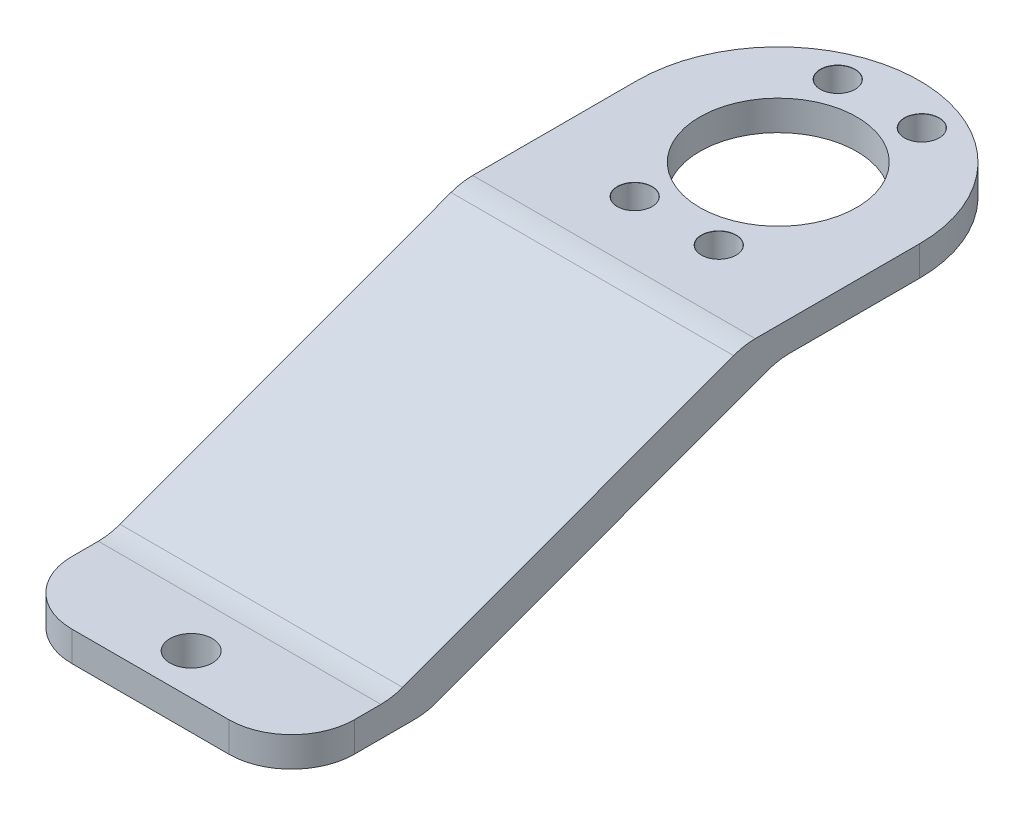
SolidWorks part; units mm, degrees
material "ABS PC"
ref_plane "Front Plane" through (0, 0, 0) normal (0, 0, 1) x (1, 0, 0)
ref_plane "Top Plane" through (0, 0, 0) normal (0, 1, 0) x (1, 0, 0)
ref_plane "Right Plane" through (0, 0, 0) normal (1, 0, 0) x (0, 0, -1)
sketch "Sketch1" plane through (0, 0, 0) normal (0, 1, 0) x (1, 0, 0)
  line L5 (-22.5, -100) -> (22.5, -100)
  line L6 (-22.5, -100) -> (-22.5, 0)
  line L8 (22.5, -100) -> (22.5, 0)
  line L9 (-22.5, -100) -> (22.5, 0) construction
  line L10 (-22.5, 0) -> (22.5, -100) construction
  arc A0 (22.5, 0) -> (-22.5, 0) centre (0, 0) ccw
  point P2 (0, -50)
  dimension "D1" = 45
  dimension "D2" = 100
  dimension "D3" = 45
extrude "Boss-Extrude1" add sketch "Sketch1" along normal blind 25.4
sketch "Sketch2" plane through (0, 25.4, 0) normal (0, 1, 0) x (1, 0, 0)
  line L0 (-6.697, 16.1679) -> (6.697, 16.1679) construction
  circle A0 centre (0, 0) radius 17.5 construction
  circle A1 centre (0, 0) radius 17.5 construction
  circle A2 centre (0, 0) radius 17.5 construction
  circle A3 centre (0, 0) radius 17.5 construction
  circle A4 centre (0, 0) radius 17.5 construction
  circle A5 centre (0, 0) radius 17.5 construction
  circle A6 centre (0, 0) radius 17.5 construction
  circle A7 centre (0, 0) radius 17.5 construction
  point P3 (-6.697, 16.1679)
  point P5 (-16.1679, -6.697)
  point P7 (6.697, 16.1679)
  point P9 (16.1679, 6.697)
  point P11 (16.1679, -6.697)
  point P13 (6.697, -16.1679)
  point P15 (-6.697, -16.1679)
  point P16 (0, 0)
  point P18 (-16.1679, 6.697)
  dimension "D1" = 35
  dimension "D2" = 8
hole_wizard "M5 Clearance Hole1" positions "Sketch3" profile "Sketch4" hole size "M5" standard "ANSI Metric" end condition through all
sketch "Sketch3" plane through (0, 25.4, 0) normal (0, 1, 0) x (1, 0, 0)
  point P0 (-6.697, -16.1679)
  point P3 (6.697, -16.1679)
  point P6 (6.697, 16.1679)
  point P15 (-6.697, 16.1679)
sketch "Sketch4" plane through (-6.697, 25.4, 16.1679) normal (1, 0, 0) x (0, 0, 1)
  line L0 (0, 0) -> (0, 25.4)
  line L1 (0, 25.4) -> (2.75, 25.4)
  line L2 (2.75, 25.4) -> (2.75, 0.025)
  line L3 (2.75, 0.025) -> (2.775, 0)
  line L5 (2.775, 0) -> (0, 0)
  line L6 (-2.75, 0.025) -> (-2.775, 0) construction
  line L11 (0, -6.35) -> (0, 107.95) construction
  dimension "Thru Hole Dia." = 5.5
  dimension "Thru Hole Depth" = 25.4
  dimension "Near C'Sink Dia." = 5.55
  dimension "Near C'Sink Angle" = 90
sketch "Sketch5" plane through (0, 25.4, 0) normal (0, 1, 0) x (1, 0, 0)
  circle A0 centre (0, 0) radius 12.5
  dimension "D1" = 25
extrude "Cut-Extrude1" cut sketch "Sketch5" against normal through all
sketch "Sketch6" plane through (0, 25.4, 0) normal (0, 1, 0) x (1, 0, 0)
  line L0 (-22.5, -100) -> (22.5, -100) construction
  circle A0 centre (0, -93.5) radius 3.3782
  dimension "D1" = 6.7564
  dimension "D2" = 6.5
extrude "Cut-Extrude2" cut sketch "Sketch6" against normal through all
sketch "Sketch7" plane through (0, 25.4, 0) normal (0, 1, 0) x (1, 0, 0)
  line L0 (12.5, -81) -> (-12.5, -81) construction
  line L1 (12.5, -85.5) -> (-12.5, -85.5)
  line L2 (12.5, -76.5) -> (-12.5, -76.5)
  line L3 (0, -93.5) -> (0, 0) construction
  line L4 (12.5, -65) -> (-12.5, -65) construction
  line L5 (12.5, -69.5) -> (-12.5, -69.5)
  line L6 (12.5, -60.5) -> (-12.5, -60.5)
  line L7 (12.5, -49) -> (-12.5, -49) construction
  line L8 (12.5, -53.5) -> (-12.5, -53.5)
  line L9 (12.5, -44.5) -> (-12.5, -44.5)
  arc A0 (12.5, -85.5) -> (12.5, -76.5) centre (12.5, -81) ccw
  arc A1 (-12.5, -76.5) -> (-12.5, -85.5) centre (-12.5, -81) ccw
  arc A2 (12.5, -69.5) -> (12.5, -60.5) centre (12.5, -65) ccw
  arc A3 (-12.5, -60.5) -> (-12.5, -69.5) centre (-12.5, -65) ccw
  arc A4 (12.5, -53.5) -> (12.5, -44.5) centre (12.5, -49) ccw
  arc A5 (-12.5, -44.5) -> (-12.5, -53.5) centre (-12.5, -49) ccw
  circle A6 centre (0, -93.5) radius 3.3782 construction
  point P2 (0, -81)
  point P15 (0, -65)
  point P22 (0, -49)
  point P28 (0, -85.5)
  dimension "D2" = 4.5
  dimension "D4" = 8
  dimension "D3" = 25
  dimension "D1" = 3
extrude "Cut-Extrude3" [suppressed] cut sketch "Sketch7" against normal through all
fillet "Fillet1" radius 10 2 edges at (22.5, 12.7, 100) (-22.5, 12.7, 100)
sketch "Sketch9" plane through (-22.5, 0, 0) normal (-1, 0, 0) x (0, 0, 1)
  line L0 (100, 25.4) -> (90, 25.4) construction
  line L1 (0, 25.4) -> (-22.5, 25.4) construction
  line L2 (0, 25.4) -> (90, 25.4) construction
  line L3 (100, 25.4) -> (90, 25.4) construction
  line L4 (0, 25.4) -> (-22.5, 25.4) construction
  line L5 (0, 25.4) -> (90, 25.4) construction
  line L11 (90, 0) -> (100, 0) construction
  line L12 (0, 0) -> (90, 0) construction
  line L13 (-22.5, 0) -> (0, 0) construction
  line L14 (90, 0) -> (100, 0) construction
  line L15 (0, 0) -> (90, 0) construction
  line L16 (-22.5, 0) -> (0, 0) construction
  line L17 (-22.5, 0) -> (-22.5, 20.6375)
  line L18 (-22.5, 20.6375) -> (22.5, 20.6375)
  line L19 (22.5, 20.6375) -> (78.5562, 0)
  line L20 (78.5562, 0) -> (-22.5, 0)
  line L21 (27.9438, 25.4) -> (84, 4.7625)
  line L22 (84, 4.7625) -> (100, 4.7625)
  line L23 (100, 4.7625) -> (100, 25.4)
  line L24 (100, 25.4) -> (27.9438, 25.4)
  dimension "D1" = 16
  dimension "D2" = 4.7625
  dimension "D3" = 6.35
  dimension "D4" = 4.7625
  dimension "D5" = 45
extrude "Cut-Extrude4" cut sketch "Sketch9" against normal through all
fillet "Fillet2" radius 10 4 edges at (0, 0, 78.5562) (0, 4.7625, 84) (0, 20.6375, 22.5) (0, 25.4, 27.9438)
